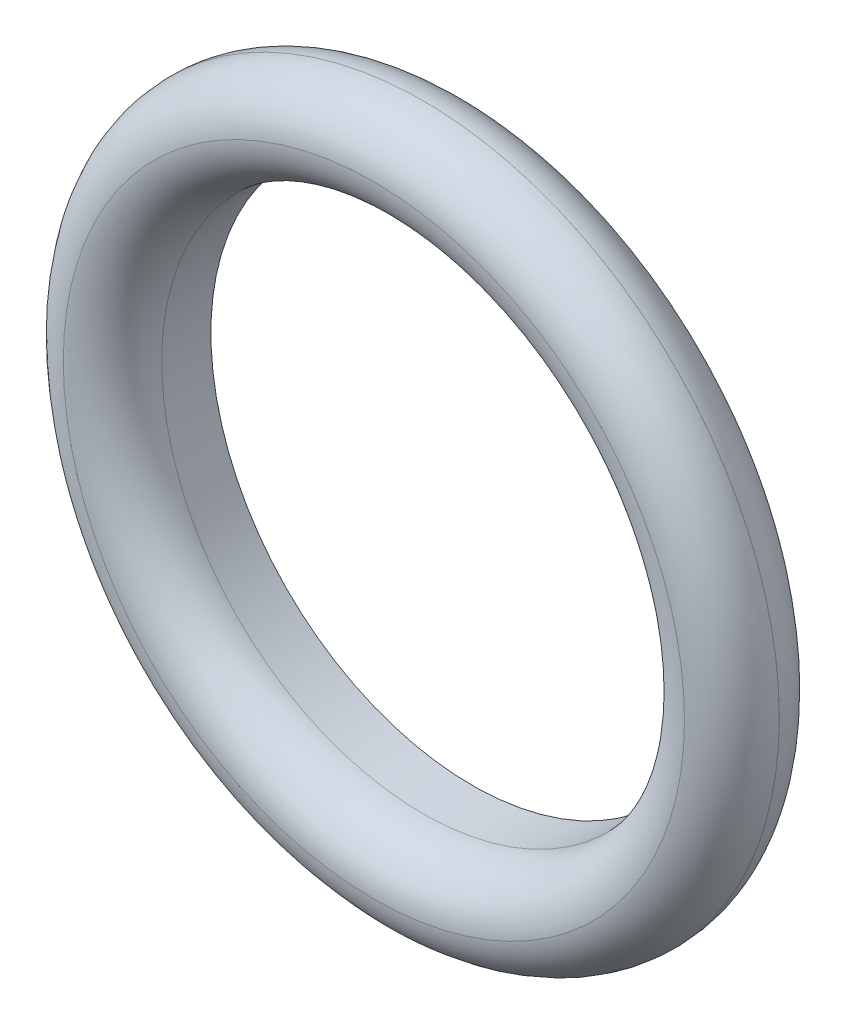
SolidWorks part; units mm, degrees
ref_plane "Front Plane" through (0, 0, 0) normal (0, 0, 1) x (1, 0, 0)
ref_plane "Top Plane" through (0, 0, 0) normal (0, 1, 0) x (1, 0, 0)
ref_plane "Right Plane" through (0, 0, 0) normal (1, 0, 0) x (0, 0, -1)
sketch "Sketch1" plane through (0, 0, 0) normal (0, 0, 1) x (1, 0, 0)
  circle A0 centre (0, 0) radius 72.4011
  circle A1 centre (0, 0) radius 53.1171
extrude "Boss-Extrude1" add sketch "Sketch1" along normal blind 20
fillet "Fillet8" radius 10 1 edges at (53.1171, 0, 20)
fillet "Fillet9" radius 10 1 edges at (72.4011, 0, 20)
fillet "Fillet10" radius 10 1 edges at (72.4011, 0, 0)
